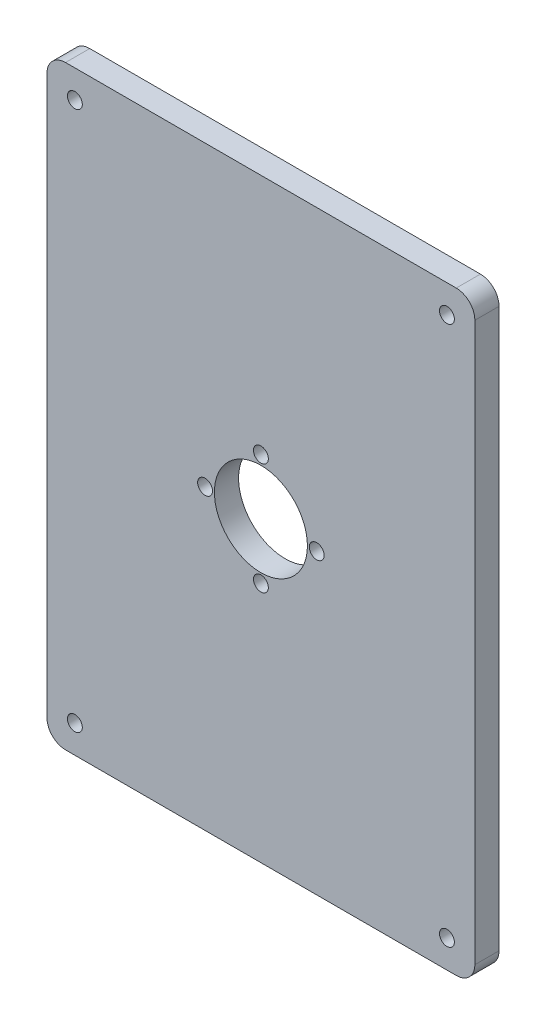
SolidWorks part; units mm, degrees
ref_plane "Alzado" through (0, 0, 0) normal (0, 0, 1) x (1, 0, 0)
ref_plane "Planta" through (0, 0, 0) normal (0, 1, 0) x (1, 0, 0)
ref_plane "Vista lateral" through (0, 0, 0) normal (1, 0, 0) x (0, 0, -1)
sketch "Croquis2" plane through (0, 0, 0) normal (0, 0, 1) x (1, 0, 0)
  line L1 (-105, 160) -> (105, 160)
  line L2 (-115, 150) -> (-115, -150)
  line L3 (-105, -160) -> (105, -160)
  line L4 (115, 150) -> (115, -150)
  line L5 (-115, 160) -> (115, -160) construction
  line L6 (-115, -160) -> (115, 160) construction
  arc A0 (105, 160) -> (115, 150) centre (105, 150) cw
  arc A1 (105, -160) -> (115, -150) centre (105, -150) ccw
  arc A2 (-115, -150) -> (-105, -160) centre (-105, -150) ccw
  arc A3 (-105, 160) -> (-115, 150) centre (-105, 150) ccw
  circle A4 centre (-100, -145) radius 4
  circle A5 centre (-100, 145) radius 4
  circle A6 centre (100, -145) radius 4
  circle A7 centre (100, 145) radius 4
  point P0 (0, 0)
  dimension "D3" = 10
  dimension "D4" = 8
  dimension "D7" = 8
  dimension "D10" = 15
  dimension "D1" = 320
  dimension "D2" = 230
  dimension "D5" = 15
  dimension "D6" = 15
  dimension "D8" = 15
  dimension "D9" = 15
extrude "Saliente-Extruir1" add sketch "Croquis2" along normal blind 13
sketch "Croquis3" plane through (0, 0, 13) normal (0, 0, 1) x (1, 0, 0)
  circle A0 centre (0, 0) radius 30
  circle A1 centre (0, 0) radius 25
  circle A2 centre (30, 0) radius 4
  circle A3 centre (0, 30) radius 4
  circle A4 centre (-30, 0) radius 4
  circle A5 centre (0, -30) radius 4
  dimension "D1" = 60
  dimension "D2" = 50
extrude "Cortar-Extruir1" cut sketch "Croquis3" against normal through all contours A1 region at (0, 0, 13)
extrude "Cortar-Extruir2" cut sketch "Croquis3<3>" against normal through all contours A4 | A3 | A2 | A5
sketch "Croquis3<3>" plane through (0, 0, 13) normal (0, 0, 1) x (1, 0, 0) same geometry as "Croquis3"
